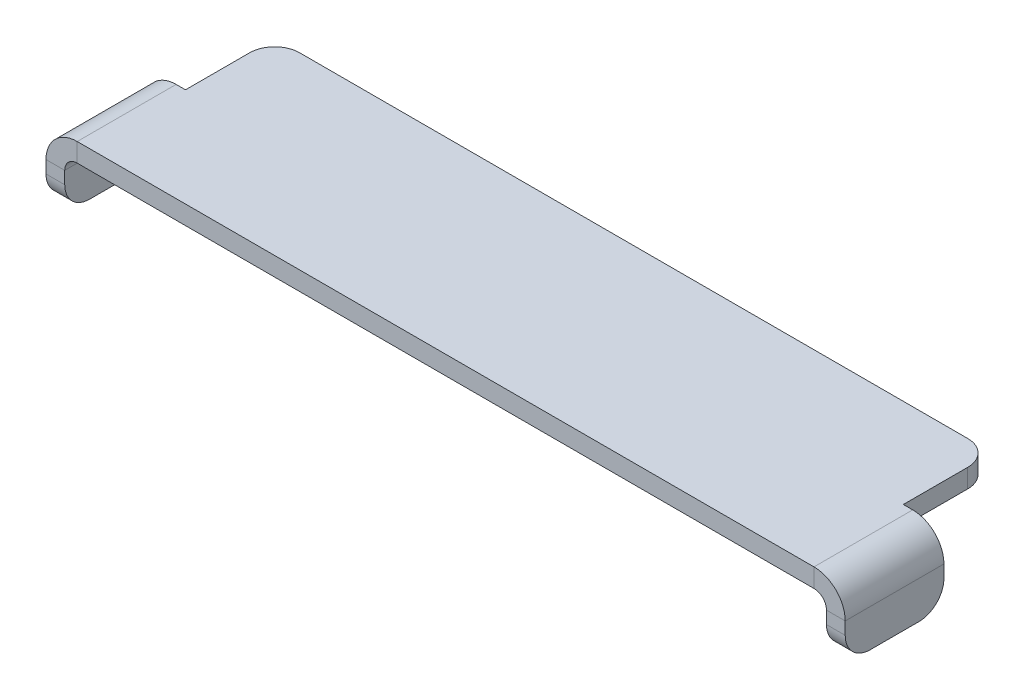
SolidWorks part; units mm, degrees
note: The reader was unsure of these and kept them because the rebuilt part matched: flange length of "Edge-Flange1".
material "Plain Carbon Steel"
ref_plane "Front" through (0, 0, 0) normal (0, 0, 1) x (1, 0, 0)
ref_plane "Top" through (0, 0, 0) normal (0, 1, 0) x (1, 0, 0)
ref_plane "Right" through (0, 0, 0) normal (1, 0, 0) x (0, 0, -1)
sketch "Sketch1" plane through (0, 0, 0) normal (0, 1, 0) x (1, 0, 0)
  line L1 (0, 0) -> (64, 0)
  line L2 (0, 0) -> (0, 15.0605)
  line L3 (0, 15.0605) -> (64, 15.0605)
  line L4 (64, 0) -> (64, 15.0605)
  line L6 (66, 16.0605) -> (64, 16.0605) construction
  point P5 (0, 0)
  dimension "D1" = 1
  dimension "D2" = 64
base flange "Base-Flange1" sketch "Sketch1" thickness 1.5 reverse thickness direction no parameters "D1"=1
edge flange "Edge-Flange1" sketch "Sketch24" flange profiles "Sketch24", "Sketch25" flange angle 90 flange length 4 flange position material inside bend radius 1 thickness 1.5 relief rectangular parameters "D1"=0.5, "D6"=10, "D8"=1
sketch "Sketch24" plane through (64, -1.5, 0) normal (1, 0, 0) x (0, 0, 1)
  line L2 (-7.9044, 0) -> (-7.9044, 4)
  line L3 (-7.9044, 4) -> (0, 4)
  line L4 (0, 4) -> (0, 0)
  line L11 (0, 0) -> (-15.0605, 0) construction
  line L12 (0, 0) -> (-7.9044, 0)
sketch "Sketch25" plane through (0, -1.5, 0) normal (-1, 0, 0) x (0, 0, -1)
  line L0 (15.0605, 0) -> (0, 0) construction
  line L1 (7.921, 0) -> (0, 0)
  line L2 (0, 0) -> (0, 4)
  line L3 (0, 4) -> (7.921, 4)
  line L4 (7.921, 4) -> (7.921, 0)
  point P5 (0, 0)
bend "EdgeBend1" bend radius 1 bend angle 90 parameters "D5"=1
bend "EdgeBend2" bend radius 1 bend angle 90 parameters "D5"=2
sketch "Sketch31" plane through (0, 0, 0) normal (0, 1, 0) x (1, 0, 0)
  line L1 (60.75, 8.6544) -> (64, 8.6544)
  line L2 (60.75, 8.6544) -> (60.75, 15.0605)
  line L3 (60.75, 15.0605) -> (64, 15.0605)
  line L4 (64, 8.6544) -> (64, 15.0605)
  line L5 (3.25, 8.671) -> (0, 8.671)
  line L6 (3.25, 8.671) -> (3.25, 15.0605)
  line L7 (3.25, 15.0605) -> (0, 15.0605)
  line L8 (0, 8.671) -> (0, 15.0605)
extrude "Cut-Extrude1" cut sketch "Sketch31" against normal blind 10 normal cut yes
fillet "Fillet1" radius 2 6 edges at (0.75, -5.5, 0) (0.75, -5.5, -7.921) (60.75, -0.75, -15.0605) (3.25, -0.75, -15.0605) (63.25, -5.5, -7.9044) (63.25, -5.5, 0)
sketch "Bend-Lines1" [suppressed] plane through (0, 0, 0) normal (0, 1, 0) x (1, 0, 0)
sketch "Bounding-Box1" [suppressed] plane through (0, 0, 0) normal (0, 1, 0) x (1, 0, 0)
hole_wizard "Ø1.0mm Dowel Slot1" [suppressed] positions "Sketch34" profile "Sketch33" size "Ø1.0" standard "ANSI Metric"
sketch "Sketch34" plane through (0, 0, 0) normal (0, 1, 0) x (1, 0, 0)
  line L0 (1.1256, 7.921) -> (1.1256, 0) construction
  line L1 (62.8744, 0) -> (62.8744, 7.9044) construction
  line L2 (1.1256, 2.4605) -> (1.1256, 5.4605) construction
  point P0 (1.1256, 3.9605)
  point P4 (62.8744, 3.9522)
  dimension "D1" = 3
sketch "Sketch33" plane through (1.1256, 0, -3.9605) normal (1, 0, 0) x (0, 0, 1)
  line L0 (0, 0) -> (0, 1.5)
  line L1 (0, 1.5) -> (0.5, 1.5)
  line L2 (0.5, 1.5) -> (0.5, 0)
  line L5 (0.5, 0) -> (0, 0)
  line L11 (0, -6.35) -> (0, 107.95) construction
  dimension "Thru Hole Dia." = 1
  dimension "Thru Hole Depth" = 1.5
sheet metal parameters "Sheet-Metal1" thickness 1.5 parameters "D1"=1.65
flat pattern "Flat-Pattern1" [suppressed]
sketch "Bend-Lines2" plane through (0, 0, 0) normal (0, 1, 0) x (1, 0, 0)
sketch3d "Bounding-Box2" [suppressed]
  line L0 (64, 7.9746, 0) -> (0, 7.9746, 0) construction
  line L1 (64, 0, 0) -> (0, 0, 0) construction
  line L2 (64, 7.9746, 0) -> (64, 0, 0) construction
  line L3 (0, 7.9746, 0) -> (0, 0, 0) construction
sheet metal parameters "Sheet-Metal8" thickness 1.5 parameters "D1"=1.65
flat pattern "Flat-Pattern1"
sketch "Bend-Lines2" plane through (0, 0, 0) normal (0, 1, 0) x (1, 0, 0)
  line L0 (1.1256, 7.921) -> (1.1256, 0) construction
  line L1 (62.8744, 0) -> (62.8744, 7.9044) construction
  line L2 (1.1256, 7.921) -> (1.1256, 0) construction
  line L3 (62.8744, 0) -> (62.8744, 7.9044) construction
sketch3d "Bounding-Box2" [suppressed]
  line L0 (66.2489, 16.0605, 0) -> (-2.2489, 16.0605, 0) construction
  line L1 (66.2489, 0, 0) -> (-2.2489, 0, 0) construction
  line L2 (66.2489, 16.0605, 0) -> (66.2489, 0, 0) construction
  line L3 (-2.2489, 16.0605, 0) -> (-2.2489, 0, 0) construction
bend of the flat pattern "Flatten-<EdgeBend1>1"
bend of the flat pattern "Flatten-<EdgeBend2>1"
sheet metal parameters "Sheet-Metal9" thickness 1.5 parameters "D1"=1.65
flat pattern "Flat-Pattern1"
sketch "Bend-Lines2" plane through (0, 0, 0) normal (0, 1, 0) x (1, 0, 0)
  line L0 (1.1256, 7.921) -> (1.1256, 0) construction
  line L1 (62.8744, 0) -> (62.8744, 7.9044) construction
  line L2 (1.1256, 7.921) -> (1.1256, 0) construction
  line L3 (62.8744, 0) -> (62.8744, 7.9044) construction
sketch3d "Bounding-Box2" [suppressed]
  line L0 (67.2489, 15.0605, 0) -> (-3.2489, 15.0605, 0) construction
  line L1 (67.2489, 0, 0) -> (-3.2489, 0, 0) construction
  line L2 (67.2489, 15.0605, 0) -> (67.2489, 0, 0) construction
  line L3 (-3.2489, 15.0605, 0) -> (-3.2489, 0, 0) construction
bend of the flat pattern "Flatten-<EdgeBend1>1"
bend of the flat pattern "Flatten-<EdgeBend2>1"
equation "\"chipper width\"= 67mm"
